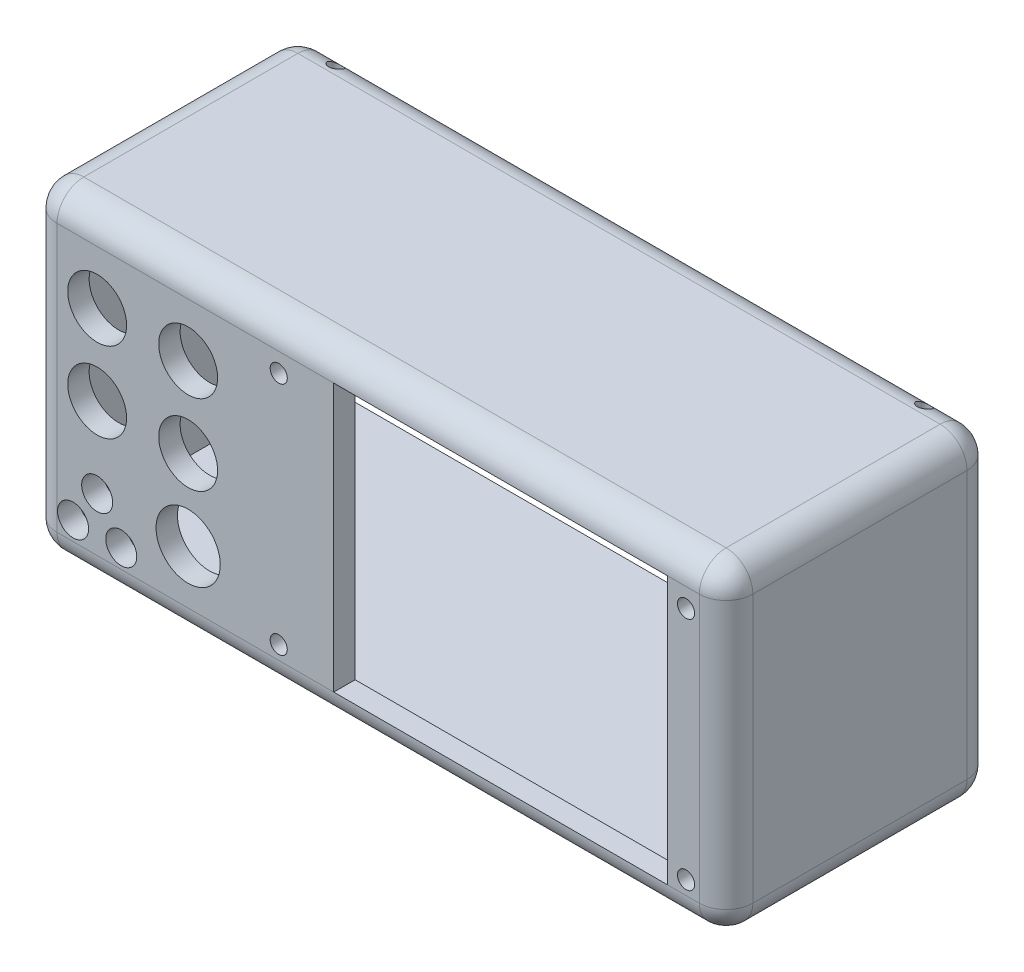
SolidWorks part; units mm, degrees
other "Markup1"
sketch "Sketch2" plane through (-61.5099, -36.0015, -50) normal (0, 0, -1) x (-1, 0, 0)
ref_plane "Front Plane" through (0, 0, 0) normal (0, 0, 1) x (1, 0, 0)
ref_plane "Top Plane" through (0, 0, 0) normal (0, 1, 0) x (1, 0, 0)
ref_plane "Right Plane" through (0, 0, 0) normal (1, 0, 0) x (0, 0, -1)
sketch "Sketch1" plane through (0, 0, 0) normal (0, 0, 1) x (1, 0, 0)
  line L0 (-61.5099, 23.9985) -> (68.4901, 23.9985)
  line L1 (68.4901, 23.9985) -> (68.4901, -36.0015)
  line L2 (68.4901, -36.0015) -> (-61.5099, -36.0015)
  line L3 (-61.5099, -36.0015) -> (-61.5099, 23.9985)
  line L8 (-22.0099, 18.9985) -> (63.9901, 18.9985)
  line L9 (63.9901, 18.9985) -> (63.9901, -31.0015)
  line L10 (63.9901, -31.0015) -> (-22.0099, -31.0015)
  line L11 (-22.0099, -31.0015) -> (-22.0099, 18.9985)
  line L12 (-4.8099, 18.9985) -> (-4.8099, -31.0015)
  line L13 (57.5901, 18.9985) -> (57.5901, -31.0015)
  line L14 (-61.5099, 19.9985) -> (68.4901, 19.9985)
  line L15 (-61.5099, -32.0015) -> (68.4901, -32.0015)
  line L16 (-57.5099, 19.9985) -> (-57.5099, -32.0015)
  line L17 (64.4901, 19.9985) -> (64.4901, -32.0015)
  circle A0 centre (-15.0899, 15.4485) radius 1.6
  circle A1 centre (-15.0899, -28.4515) radius 1.6
  circle A2 centre (61.0101, 15.4485) radius 1.6
  circle A3 centre (61.0101, -28.4515) radius 1.6
  circle A4 centre (-49.0099, 8.9985) radius 5.5
  circle A5 centre (-32.0099, 8.9985) radius 5.5
  circle A6 centre (-49.0099, -6.0015) radius 5.5
  circle A7 centre (-32.0099, -6.0015) radius 5.5
  circle A8 centre (-32.0099, -21.0015) radius 6
  circle A9 centre (-49.0099, -21.0015) radius 2.9
  circle A10 centre (-53.5099, -27.5015) radius 2.9
  circle A11 centre (0, 0) radius 2.9
  circle A12 centre (-44.5099, -27.5015) radius 2.9
  dimension "D8" = 3.2
  dimension "D10" = 3.2
  dimension "D15" = 3.2
  dimension "D18" = 3.2
  dimension "D21" = 11
  dimension "D30" = 12
  dimension "D33" = 5.8
  dimension "D16" = 4.5
  dimension "D1" = 130
  dimension "D2" = 60
  dimension "D3" = 50
  dimension "D4" = 6.4
  dimension "D5" = 86
  dimension "D6" = 17.2
  dimension "D7" = 76.1
  dimension "D9" = 76.1
  dimension "D11" = 43.9
  dimension "D12" = 43.9
  dimension "D13" = 3.55
  dimension "D14" = 3.55
  dimension "D17" = 4
  dimension "D19" = 5
  dimension "D20" = 4.5
  dimension "D22" = 10
  dimension "D23" = 27
  dimension "D24" = 15
  dimension "D25" = 15
  dimension "D26" = 30
  dimension "D27" = 27
  dimension "D28" = 10
  dimension "D29" = 30
  dimension "D31" = 10
  dimension "D32" = 45
  dimension "D34" = 45
  dimension "D35" = 13
  dimension "D36" = 4
  dimension "D37" = 4
  dimension "D38" = 4
  dimension "D39" = 4
  dimension "D40" = 4.5
extrude "Boss-Extrude1" add sketch "Sketch1" against normal blind 4 contours L3 L2 L1 L0 A9 A8 A7 A6 A5 A4 L10 L11 L8 L9 | L12 L8 L11 L10 A1 A0 | L8 L13 L10 L9 A3 A2 region at (3.4901, 19.8658, 0) region at (-13.3779, -5.992, 0) region at (60.7784, -5.9751, 0)
extrude "Boss-Extrude2" add sketch "Sketch1<3>" against normal blind 50 contours L3 L14 L1 L0 | L16 L14 L3 L15 | L14 L17 L15 L1 | L15 L3 L2 L1 region at (3.4901, 21.9985, 0) region at (-59.5099, -6.0015, 0) region at (66.4901, -6.0015, 0) region at (3.4901, -34.0015, 0)
sketch "Sketch1<3>" plane through (0, 0, 0) normal (0, 0, 1) x (1, 0, 0) same geometry as "Sketch1"
sketch "Sketch3" plane through (0, 23.9985, 0) normal (0, 1, 0) x (1, 0, 0)
  line L0 (-61.5099, 50) -> (-61.5099, 0) construction
  line L1 (68.4901, 50) -> (68.4901, 0) construction
  line L2 (-61.5099, 50) -> (68.4901, 50) construction
  circle A0 centre (-51.5099, 47) radius 1.25
  circle A1 centre (58.4901, 47) radius 1.25
  dimension "D1" = 2.5
  dimension "D2" = 10
  dimension "D3" = 10
  dimension "D4" = 3
  dimension "D5" = 3
extrude "Cut-Extrude1" cut sketch "Sketch3" against normal through all
fillet "Fillet2" radius 5 1 edges at (-61.5099, -6.0015, 0)
fillet "Fillet3" radius 5 1 edges at (68.4901, -6.0015, 0)
fillet "Fillet4" radius 5 5 edges at (-61.5099, 23.9985, -27.5) (-60.0454, 23.9985, -1.4645) (68.4901, 23.9985, -27.5) (67.0256, 23.9985, -1.4645) (3.4901, 23.9985, 0)
fillet "Fillet5" radius 5 5 edges at (68.4901, -36.0015, -27.5) (67.0256, -36.0015, -1.4645) (-61.5099, -36.0015, -27.5) (-60.0454, -36.0015, -1.4645) (3.4901, -36.0015, 0)
fillet "Fillet6" radius 5 8 edges at (-60.0454, 22.534, -50) (-61.5099, -6.0015, -50) (-60.0454, -34.5371, -50) (3.4901, -36.0015, -50) (67.0256, -34.5371, -50) (68.4901, -6.0015, -50) (67.0256, 22.534, -50) (3.4901, 23.9985, -50)
